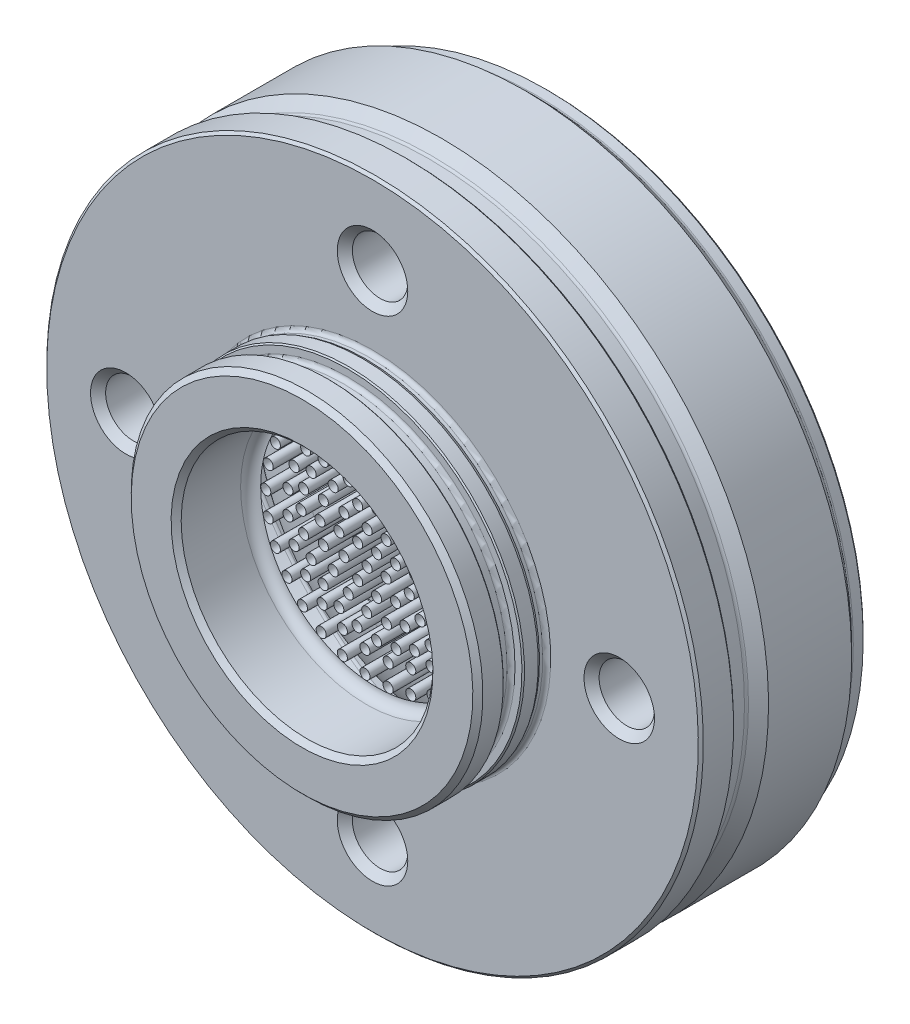
SolidWorks part; units mm, degrees
material "4140 H/T"
ref_plane "Front Plane" through (0, 0, 0) normal (0, 0, 1) x (1, 0, 0)
ref_plane "Top Plane" through (0, 0, 0) normal (0, 1, 0) x (1, 0, 0)
ref_plane "Right Plane" through (0, 0, 0) normal (1, 0, 0) x (0, 0, -1)
sketch "Sketch1" plane through (0, 0, 0) normal (1, 0, 0) x (0, 0, -1)
  line L0 (0, 50.5) -> (0, 62.55)
  line L1 (-0.5, 63.05) -> (-2.4686, 63.05)
  line L2 (-23.7314, 62.7) -> (-27.1, 62.7)
  line L3 (-39.65, 34.925) -> (-39.9, 34.675)
  line L4 (-3.0343, 63.2843) -> (-4.675, 64.925)
  line L5 (-4.675, 64.925) -> (-21.175, 64.925)
  line L6 (-21.175, 64.925) -> (-23.1657, 62.9343)
  line L7 (-43.6, 34.675) -> (-43.85, 34.925)
  line L12 (-27.9, 63.5) -> (-27.9, 64.7)
  line L13 (-28.4, 65.2) -> (-34.4, 65.2)
  line L14 (-34.9, 64.7) -> (-34.9, 35.4)
  line L15 (-36.9, 34.925) -> (-39.65, 34.925)
  line L16 (-39.9, 34.675) -> (-39.9, 33.3)
  line L17 (-40.7, 32.5) -> (-42.8, 32.5)
  line L18 (-43.6, 33.3) -> (-43.6, 34.675)
  line L19 (-43.85, 34.925) -> (-47.9, 34.925)
  line L20 (-47.9, 34.925) -> (-48.9, 33.925)
  line L21 (-48.9, 33.925) -> (-48.9, 26)
  line L22 (-48.9, 26) -> (-47.9, 25)
  line L23 (-47.9, 25) -> (-36.1, 25)
  line L24 (-34.1, 23) -> (-34.1, 0)
  line L25 (-34.1, 0) -> (-24.8, 0)
  line L26 (0, 0) -> (-24.8, 0) construction
  line L27 (-24.8, 0) -> (-24.8, 23.5898)
  line L28 (-36.9, 34.925) -> (-36.3371, 34.6)
  line L29 (-36.3371, 34.6) -> (-35.7, 34.6)
  line L30 (-34.4, 65.2) -> (-34.9, 64.7)
  line L31 (-27.9, 64.7) -> (-28.4, 65.2)
  line L32 (0, 62.55) -> (-0.5, 63.05)
  arc A0 (-24.8, 23.5898) -> (-2.7556, 47.51) centre (-0.8, 23.5898) cw
  arc A1 (-40.7, 32.5) -> (-39.9, 33.3) centre (-40.7, 33.3) ccw
  arc A2 (-36.1, 25) -> (-34.1, 23) centre (-36.1, 23) cw
  arc A3 (-23.7314, 62.7) -> (-23.1657, 62.9343) centre (-23.7314, 63.5) ccw
  arc A4 (-27.9, 63.5) -> (-27.1, 62.7) centre (-27.1, 63.5) ccw
  arc A5 (-3.0343, 63.2843) -> (-2.4686, 63.05) centre (-2.4686, 63.85) ccw
  arc A6 (0, 50.5) -> (-2.7556, 47.51) centre (-3, 50.5) cw
  arc A7 (-43.6, 33.3) -> (-42.8, 32.5) centre (-42.8, 33.3) ccw
  arc A8 (-35.7, 34.6) -> (-34.9, 35.4) centre (-35.7, 35.4) ccw
  point P1 (0, 63.05)
  point P9 (-23.4, 62.7)
  point P14 (-27.9, 65.2)
  point P15 (-34.9, 65.2)
  point P17 (-39.9, 34.925)
  point P20 (-43.6, 34.925)
  point P44 (-2.8, 63.05)
  dimension "D3" = 2
  dimension "D31" = 0.8
  dimension "D32" = 3
  dimension "D35" = 0.8
  dimension "D34" = 27.9
  dimension "D9" = 24
  dimension "D39" = 0.8
  dimension "D1" = 129.85
  dimension "D2" = 48.9
  dimension "D4" = 14.8
  dimension "D5" = 50
  dimension "D6" = 69.85
  dimension "D7" = 130.4
  dimension "D8" = 24.8
  dimension "D10" = 34.9
  dimension "D11" = 65
  dimension "D12" = 3.7
  dimension "D13" = 5
  dimension "D14" = 69.2
  dimension "D15" = 2
  dimension "D16" = 30
  dimension "D17" = 45
  dimension "D18" = 1
  dimension "D19" = 45
  dimension "D20" = 1
  dimension "D21" = 126.1
  dimension "D22" = 45
  dimension "D26" = 2.8
  dimension "D27" = 23.4
  dimension "D28" = 125.4
  dimension "D29" = 45
  dimension "D30" = 7
  dimension "D33" = 101
  dimension "D36" = 5
revolve "Revolve1" add sketch "Sketch1" angle 360 about L26
cosmetic thread "Cosmetic Thread1" parameters "D1"=20.1314, "D2"=126.4
sketch "Sketch2" plane through (0, 0, 34.1) normal (0, 0, 1) x (1, 0, 0)
  line L0 (0, 0) -> (30.4028, 0) construction
  line L1 (0, 0) -> (29.6667, -3.9057) construction
  circle A0 centre (0, 0) radius 3.75 construction
  circle A1 centre (0, 0) radius 7.5 construction
  circle A2 centre (0, 0) radius 11.25 construction
  circle A3 centre (0, 0) radius 15 construction
  circle A5 centre (0, 0) radius 17.75 construction
  circle A6 centre (0, 0) radius 22 construction
  point P0 (0, 0)
  point P1 (3.75, 0)
  point P3 (7.5, 0)
  point P4 (11.25, 0)
  point P5 (15, 0)
  point P7 (22, 0)
  point P8 (17.5981, -2.3168)
  point P19 (1.875, -3.2476)
  point P20 (-1.875, -3.2476)
  point P21 (-3.75, 0)
  point P22 (-1.875, 3.2476)
  point P23 (1.875, 3.2476)
  point P24 (6.4952, -3.75)
  point P25 (3.75, -6.4952)
  point P26 (0, -7.5)
  point P27 (-3.75, -6.4952)
  point P28 (-6.4952, -3.75)
  point P29 (-7.5, 0)
  point P30 (-6.4952, 3.75)
  point P31 (-3.75, 6.4952)
  point P32 (0, 7.5)
  point P33 (3.75, 6.4952)
  point P34 (6.4952, 3.75)
  point P35 (10.5715, -3.8477)
  point P36 (8.618, -7.2314)
  point P37 (5.625, -9.7428)
  point P38 (1.9535, -11.0791)
  point P39 (-1.9535, -11.0791)
  point P40 (-5.625, -9.7428)
  point P41 (-8.618, -7.2314)
  point P42 (-10.5715, -3.8477)
  point P43 (-11.25, 0)
  point P44 (-10.5715, 3.8477)
  point P45 (-8.618, 7.2314)
  point P46 (-5.625, 9.7428)
  point P47 (-1.9535, 11.0791)
  point P48 (1.9535, 11.0791)
  point P49 (5.625, 9.7428)
  point P50 (8.618, 7.2314)
  point P51 (10.5715, 3.8477)
  point P52 (14.4889, -3.8823)
  point P53 (12.9904, -7.5)
  point P54 (10.6066, -10.6066)
  point P55 (7.5, -12.9904)
  point P56 (3.8823, -14.4889)
  point P57 (0, -15)
  point P58 (-3.8823, -14.4889)
  point P59 (-7.5, -12.9904)
  point P60 (-10.6066, -10.6066)
  point P61 (-12.9904, -7.5)
  point P62 (-14.4889, -3.8823)
  point P63 (-15, 0)
  point P64 (-14.4889, 3.8823)
  point P65 (-12.9904, 7.5)
  point P66 (-10.6066, 10.6066)
  point P67 (-7.5, 12.9904)
  point P68 (-3.8823, 14.4889)
  point P69 (0, 15)
  point P70 (3.8823, 14.4889)
  point P71 (7.5, 12.9904)
  point P72 (10.6066, 10.6066)
  point P73 (12.9904, 7.5)
  point P74 (14.4889, 3.8823)
  point P75 (16.3989, -6.7926)
  point P76 (14.082, -10.8055)
  point P77 (10.8055, -14.082)
  point P78 (6.7926, -16.3989)
  point P79 (2.3168, -17.5981)
  point P80 (-2.3168, -17.5981)
  point P81 (-6.7926, -16.3989)
  point P82 (-10.8055, -14.082)
  point P83 (-14.082, -10.8055)
  point P84 (-16.3989, -6.7926)
  point P85 (-17.5981, -2.3168)
  point P86 (-17.5981, 2.3168)
  point P87 (-16.3989, 6.7926)
  point P88 (-14.082, 10.8055)
  point P89 (-10.8055, 14.082)
  point P90 (-6.7926, 16.3989)
  point P91 (-2.3168, 17.5981)
  point P92 (2.3168, 17.5981)
  point P93 (6.7926, 16.3989)
  point P94 (10.8055, 14.082)
  point P95 (14.082, 10.8055)
  point P96 (16.3989, 6.7926)
  point P97 (17.5981, 2.3168)
  point P98 (21.5192, -4.5741)
  point P99 (20.098, -8.9482)
  point P100 (17.7984, -12.9313)
  point P101 (14.7209, -16.3492)
  point P102 (11, -19.0526)
  point P103 (6.7984, -20.9232)
  point P104 (2.2996, -21.8795)
  point P105 (-2.2996, -21.8795)
  point P106 (-6.7984, -20.9232)
  point P107 (-11, -19.0526)
  point P108 (-14.7209, -16.3492)
  point P109 (-17.7984, -12.9313)
  point P110 (-20.098, -8.9482)
  point P111 (-21.5192, -4.5741)
  point P112 (-22, 0)
  point P113 (-21.5192, 4.5741)
  point P114 (-20.098, 8.9482)
  point P115 (-17.7984, 12.9313)
  point P116 (-14.7209, 16.3492)
  point P117 (-11, 19.0526)
  point P118 (-6.7984, 20.9232)
  point P119 (-2.2996, 21.8795)
  point P120 (2.2996, 21.8795)
  point P121 (6.7984, 20.9232)
  point P122 (11, 19.0526)
  point P123 (14.7209, 16.3492)
  point P124 (17.7984, 12.9313)
  point P125 (20.098, 8.9482)
  point P126 (21.5192, 4.5741)
  dimension "D2" = 7.5
  dimension "D3" = 15
  dimension "D4" = 22.5
  dimension "D5" = 30
  dimension "D6" = 44
  dimension "D7" = 35.5
  dimension "D1" = 7.5
ref_axis "Axis1" through (0, 0, 36.1) along (0, 0, 1)
hole_wizard "M2.0 (2) Diameter Hole5" positions "Sketch14" profile "Sketch13" hole size "M2.0" standard "Ansi Metric" end condition up to next
sketch "Sketch14" plane through (0, 0, 34.1) normal (0, 0, 1) x (1, 0, 0)
  point P0 (0, 0)
  point P1 (3.75, 0)
  point P3 (7.5, 0)
  point P5 (11.25, 0)
  point P7 (15, 0)
  point P9 (22, 0)
  point P11 (17.5981, 2.3168)
  point P13 (1.875, 3.2476)
  point P15 (-1.875, 3.2476)
  point P17 (-3.75, 0)
  point P19 (-1.875, -3.2476)
  point P21 (1.875, -3.2476)
  point P23 (6.4952, 3.75)
  point P25 (3.75, 6.4952)
  point P27 (0, 7.5)
  point P29 (-3.75, 6.4952)
  point P31 (-6.4952, 3.75)
  point P33 (-7.5, 0)
  point P35 (-6.4952, -3.75)
  point P37 (-3.75, -6.4952)
  point P39 (0, -7.5)
  point P41 (3.75, -6.4952)
  point P43 (6.4952, -3.75)
  point P45 (10.5715, 3.8477)
  point P47 (8.618, 7.2314)
  point P49 (5.625, 9.7428)
  point P51 (1.9535, 11.0791)
  point P53 (-1.9535, 11.0791)
  point P55 (-5.625, 9.7428)
  point P57 (-8.618, 7.2314)
  point P59 (-10.5715, 3.8477)
  point P61 (-11.25, 0)
  point P63 (-10.5715, -3.8477)
  point P65 (-8.618, -7.2314)
  point P67 (-5.625, -9.7428)
  point P69 (-1.9535, -11.0791)
  point P71 (1.9535, -11.0791)
  point P73 (5.625, -9.7428)
  point P75 (8.618, -7.2314)
  point P77 (10.5715, -3.8477)
  point P79 (14.4889, 3.8823)
  point P81 (12.9904, 7.5)
  point P83 (10.6066, 10.6066)
  point P85 (7.5, 12.9904)
  point P87 (3.8823, 14.4889)
  point P89 (0, 15)
  point P91 (-3.8823, 14.4889)
  point P93 (-7.5, 12.9904)
  point P95 (-10.6066, 10.6066)
  point P97 (-12.9904, 7.5)
  point P99 (-14.4889, 3.8823)
  point P101 (-15, 0)
  point P103 (-14.4889, -3.8823)
  point P105 (-12.9904, -7.5)
  point P107 (-10.6066, -10.6066)
  point P109 (-7.5, -12.9904)
  point P111 (-3.8823, -14.4889)
  point P113 (0, -15)
  point P115 (3.8823, -14.4889)
  point P117 (7.5, -12.9904)
  point P119 (10.6066, -10.6066)
  point P121 (12.9904, -7.5)
  point P123 (14.4889, -3.8823)
  point P125 (16.3989, 6.7926)
  point P127 (14.082, 10.8055)
  point P129 (10.8055, 14.082)
  point P131 (6.7926, 16.3989)
  point P133 (2.3168, 17.5981)
  point P135 (-2.3168, 17.5981)
  point P137 (-6.7926, 16.3989)
  point P139 (-10.8055, 14.082)
  point P141 (-14.082, 10.8055)
  point P143 (-16.3989, 6.7926)
  point P145 (-17.5981, 2.3168)
  point P147 (-17.5981, -2.3168)
  point P149 (-16.3989, -6.7926)
  point P151 (-14.082, -10.8055)
  point P153 (-10.8055, -14.082)
  point P155 (-6.7926, -16.3989)
  point P157 (-2.3168, -17.5981)
  point P159 (2.3168, -17.5981)
  point P161 (6.7926, -16.3989)
  point P163 (10.8055, -14.082)
  point P165 (14.082, -10.8055)
  point P167 (16.3989, -6.7926)
  point P169 (17.5981, -2.3168)
  point P171 (21.5192, -4.5741)
  point P173 (20.098, -8.9482)
  point P175 (17.7984, -12.9313)
  point P177 (14.7209, -16.3492)
  point P179 (11, -19.0526)
  point P181 (6.7984, -20.9232)
  point P183 (2.2996, -21.8795)
  point P185 (-2.2996, -21.8795)
  point P187 (-6.7984, -20.9232)
  point P189 (-11, -19.0526)
  point P191 (-14.7209, -16.3492)
  point P193 (-17.7984, -12.9313)
  point P195 (-20.098, -8.9482)
  point P197 (-21.5192, -4.5741)
  point P199 (-22, 0)
  point P201 (-21.5192, 4.5741)
  point P203 (-20.098, 8.9482)
  point P205 (-17.7984, 12.9313)
  point P207 (-14.7209, 16.3492)
  point P209 (-11, 19.0526)
  point P211 (-6.7984, 20.9232)
  point P213 (-2.2996, 21.8795)
  point P215 (2.2996, 21.8795)
  point P217 (6.7984, 20.9232)
  point P219 (11, 19.0526)
  point P221 (14.7209, 16.3492)
  point P223 (17.7984, 12.9313)
  point P225 (20.098, 8.9482)
  point P227 (21.5192, 4.5741)
sketch "Sketch13" plane through (0, 0, 34.1) normal (1, 0, 0) x (0, -1, 0)
  line L0 (0, 0) -> (0, 9.3)
  line L1 (0, 9.3) -> (1.1, 9.3)
  line L2 (1, 9.2) -> (1, 0)
  line L5 (1, 0) -> (0, 0)
  line L7 (1.1, 9.3) -> (1, 9.2)
  line L8 (-1.1, 9.3) -> (-1, 9.2) construction
  line L11 (0, -6.35) -> (0, 107.95) construction
  dimension "Thru Hole Dia." = 2
  dimension "Thru Hole Depth" = 9.3
  dimension "Far C'Sink Dia." = 2.2
  dimension "Far C'Sink Angle" = 90
sketch "Sketch15" plane through (0, 0, 34.9) normal (0, 0, 1) x (1, 0, 0)
  line L0 (0, 0) -> (70.0011, 0) construction
  circle A0 centre (0, 0) radius 49 construction
  point P4 (49, 0)
  point P8 (0, -49)
  point P9 (-49, 0)
  point P10 (0, 49)
  dimension "D1" = 98
hole_wizard "Ø11.0 (11) Diameter Hole1" positions "Sketch17" profile "Sketch16" hole size "Ø11.0" standard "ANSI Metric"
sketch "Sketch17" plane through (0, 0, 34.9) normal (0, 0, 1) x (1, 0, 0)
  point P1 (49, 0)
  point P2 (0, -49)
  point P4 (-49, 0)
  point P6 (0, 49)
sketch "Sketch16" plane through (49, 0, 34.9) normal (1, 0, 0) x (0, -1, 0)
  line L0 (0, 0) -> (0, 15.8047)
  line L1 (0, 15.8047) -> (5.5, 12.5)
  line L2 (5.5, 12.5) -> (5.5, 1.5)
  line L3 (5.5, 1.5) -> (7, 0)
  line L5 (7, 0) -> (0, 0)
  line L6 (-5.5, 1.5) -> (-7, 0) construction
  line L10 (0, 15.8047) -> (-5.5, 12.5) construction
  line L11 (0, -6.35) -> (0, 107.95) construction
  dimension "Hole Dia." = 11
  dimension "Hole Depth" = 12.5
  dimension "Near C'Sink Dia." = 14
  dimension "Near C'Sink Angle" = 90
  dimension "Drill Angle" = 118
sketch "Sketch18" plane through (0, 0, 34.9) normal (0, 0, 1) x (1, 0, 0)
  line L0 (0, 0) -> (-74.7152, 0) construction
  line L1 (0, 0) -> (0, -71.1316) construction
  line L2 (0, 0) -> (82.8113, 0) construction
  line L3 (0, 0) -> (-45.0534, -31.5467) construction
  arc A0 (0, -48) -> (48, 0) centre (0, 0) ccw construction
  arc A1 (-55, 0) -> (-45.0534, -31.5467) centre (0, 0) ccw construction
  text T0 "63741166 - I\r\n11111 - XX" font "Century Gothic" height 4
  dimension "D1" = 48
  dimension "D2" = 55
  dimension "D3" = 35
sketch_block_instance "SKETCH LOGO-1"
sketch_block "SKETCH LOGO" parameters "D1"=29.059, "D2"=11.4163, "D3"=29.624, "D4"=6.8884
sketch "Sketch19" plane through (0, 0, 0) normal (0, 0, -1) x (-1, 0, 0)
  circle A0 centre (0, 0) radius 63.75
  dimension "D1" = 127.5
curve "Helix/Spiral1" [suppressed] pitch 3 height 25.5 turns 8.5
sketch "Sketch20" plane through (0, 0, 0) normal (1, 0, 0) x (0, 0, -1)
  line L0 (0, 67.1118) -> (0, 55.4297) construction
  line L1 (0, -62.55) -> (0, 62.55) construction
  line L2 (0, 65) -> (1.2038, 65) construction
  line L3 (0, 0) -> (41.272, 0) construction
  line L4 (0, 65) -> (-0.8792, 63.4772)
  line L6 (-1.1872, 63.4772) -> (-2.0664, 65)
  line L7 (-1.7416, 64.4375) -> (-0.3248, 64.4375) construction
  line L8 (-1.0332, 63.1209) -> (-1.0332, 65.6985) construction
  line L11 (0.3645, 66.2475) -> (-2.4309, 66.2475)
  line L12 (-1.1872, 63.4772) -> (-0.8792, 63.4772)
  line L13 (0, 65) -> (0.3645, 65)
  line L14 (0.3645, 65) -> (0.3645, 66.2475)
  line L15 (-2.4309, 65) -> (-2.4309, 66.2475)
  line L16 (-2.4309, 65) -> (-2.0664, 65)
  dimension "D4" = 130
  dimension "D1" = 60
  dimension "D2" = 0.308
  dimension "D3" = 1.5228
  dimension "D5" = 2.7954
  dimension "D6" = 0.5625
  dimension "D7" = 1.2475
  dimension "D8" = 126.9543
sweep "Cut-Sweep1" [suppressed] cut profiles "Sketch20" path "Helix/Spiral1"
sketch "Sketch22" [suppressed] plane through (0, 0, 0) normal (0, 0, -1) x (-1, 0, 0)
  line L0 (0, 63.6) -> (0, 68.6)
  arc A0 (-21.0267, -60.0237) -> (-22.6797, -64.7425) centre (-21.8532, -62.3831) ccw
  arc A1 (-21.0267, -60.0237) -> (0, 63.6) centre (0, 0) ccw
  arc A2 (-22.6797, -64.7425) -> (0, 68.6) centre (0, 0) ccw
  dimension "D1" = 127.2
  dimension "D2" = 5
